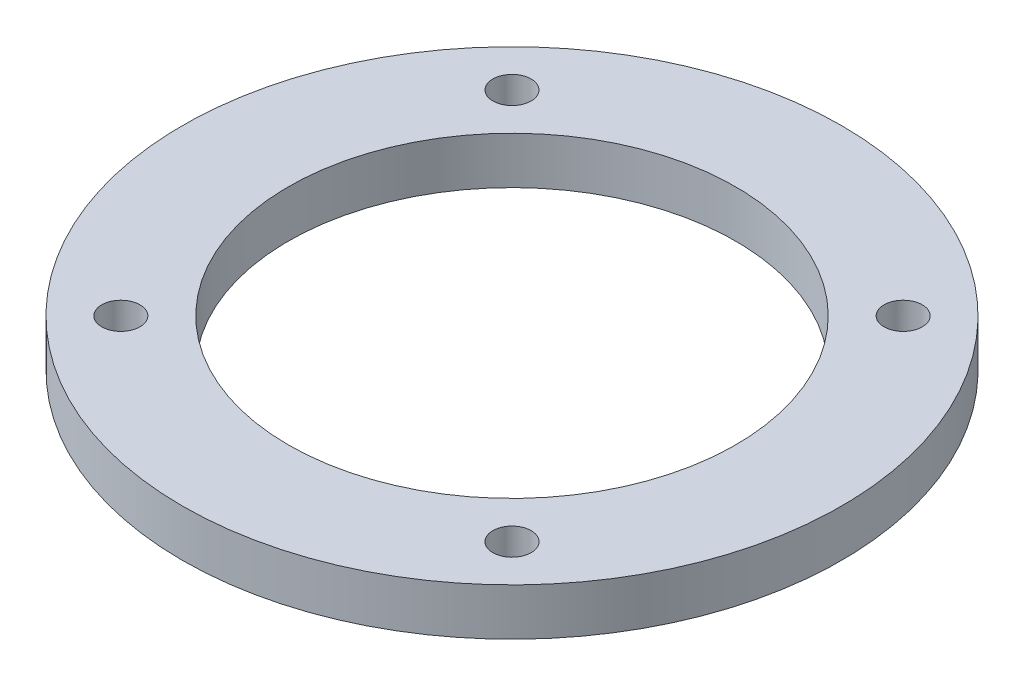
SolidWorks part; units mm, degrees
ref_plane "Front Plane" through (0, 0, 0) normal (0, 0, 1) x (1, 0, 0)
ref_plane "Top Plane" through (0, 0, 0) normal (0, 1, 0) x (1, 0, 0)
ref_plane "Right Plane" through (0, 0, 0) normal (1, 0, 0) x (0, 0, -1)
sketch "Sketch1" plane through (0, 0, 0) normal (0, 1, 0) x (1, 0, 0)
  line L1 (-88.9, -88.9) -> (88.9, -88.9)
  line L2 (-88.9, -88.9) -> (-88.9, 88.9)
  line L3 (-88.9, 88.9) -> (88.9, 88.9)
  line L4 (88.9, -88.9) -> (88.9, 88.9)
  line L5 (-88.9, -88.9) -> (88.9, 88.9) construction
  line L6 (-88.9, 88.9) -> (88.9, -88.9) construction
  point P0 (0, 0)
  dimension "D1" = 177.8
extrude "Boss-Extrude1" add sketch "Sketch1" along normal blind 12.7
sketch "Sketch2" plane through (0, 12.7, 0) normal (0, 1, 0) x (1, 0, 0)
  line L1 (-52.759, -52.759) -> (52.759, -52.759) construction
  line L2 (-52.759, -52.759) -> (-52.759, 52.759) construction
  line L3 (-52.759, 52.759) -> (52.759, 52.759) construction
  line L4 (52.759, -52.759) -> (52.759, 52.759) construction
  line L5 (-52.759, -52.759) -> (52.759, 52.759) construction
  line L6 (-52.759, 52.759) -> (52.759, -52.759) construction
  circle A0 centre (0, 0) radius 74.6125 construction
  point P3 (-52.759, 52.759)
  point P4 (52.759, 52.759)
  point P5 (52.759, -52.759)
  point P6 (-52.759, -52.759)
  dimension "D1" = 149.225
hole_wizard "13/32 (0.40625) Diameter Hole1" positions "3DSketch1" profile "Sketch3" hole size "13/32" standard "ANSI Inch"
sketch3d "3DSketch1"
  point P0 (-52.759, 12.7, -52.759)
  point P3 (52.759, 12.7, -52.759)
  point P6 (52.759, 12.7, 52.759)
  point P9 (-52.759, 12.7, 52.759)
sketch "Sketch3" plane through (-52.759, 12.7, -52.759) normal (1, 0, 0) x (0, 0, 1)
  line L0 (0, 0) -> (0, 28.5001)
  line L1 (0, 28.5001) -> (5.1594, 25.4)
  line L2 (5.1594, 25.4) -> (5.1594, 0)
  line L5 (5.1594, 0) -> (0, 0)
  line L10 (0, 28.5001) -> (-5.1594, 25.4) construction
  line L11 (0, -6.35) -> (0, 107.95) construction
  dimension "Hole Dia." = 10.3187
  dimension "Hole Depth" = 25.4
  dimension "Drill Angle" = 118
sketch "Sketch4" plane through (0, 12.7, 0) normal (0, 1, 0) x (1, 0, 0)
  circle A0 centre (0, 0) radius 60.325
  dimension "D1" = 120.65
extrude "Cut-Extrude1" cut sketch "Sketch4" against normal through all
sketch "Sketch5" plane through (0, 12.7, 0) normal (0, 1, 0) x (1, 0, 0)
  line L0 (88.9, 88.9) -> (-88.9, 88.9) construction
  circle A0 centre (0, 0) radius 88.9
extrude "Cut-Extrude2" cut sketch "Sketch5" against normal blind 12.7 flip side to cut
